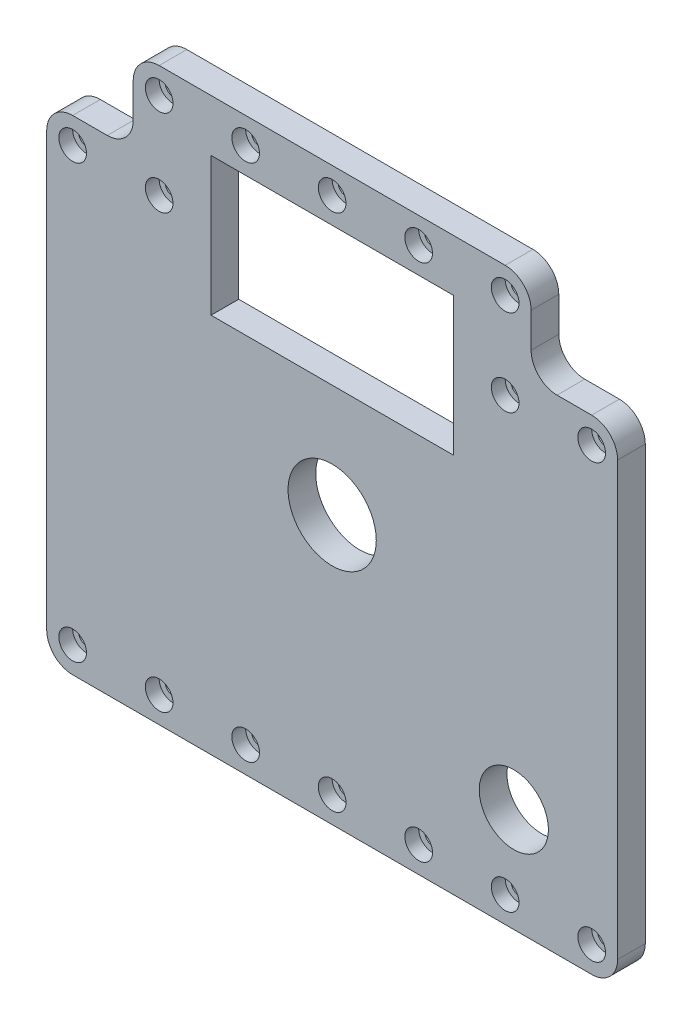
SolidWorks part; units mm, degrees
ref_plane "Front Plane" through (0, 0, 0) normal (0, 0, 1) x (1, 0, 0)
ref_plane "Top Plane" through (0, 0, 0) normal (0, 1, 0) x (1, 0, 0)
ref_plane "Right Plane" through (0, 0, 0) normal (1, 0, 0) x (0, 0, -1)
sketch "Sketch1" plane through (0, 0, 0) normal (0, 0, 1) x (1, 0, 0)
  line L0 (0, 101.5529) -> (0, -112.0648) construction
  line L1 (-50, 67.5) -> (50, 67.5)
  line L2 (57.5, 60) -> (57.5, 50)
  line L3 (65, 42.5) -> (75, 42.5)
  line L4 (82.5, 35) -> (82.5, -90)
  line L5 (75, -97.5) -> (-75, -97.5)
  line L6 (-82.5, -90) -> (-82.5, 35)
  line L7 (-75, 42.5) -> (-65, 42.5)
  line L8 (-57.5, 50) -> (-57.5, 60)
  line L9 (-35, 52.5) -> (-35, 12.5)
  line L10 (-35, 12.5) -> (35, 12.5)
  line L11 (35, 12.5) -> (35, 52.5)
  line L12 (35, 52.5) -> (-35, 52.5)
  arc A0 (-75, 42.5) -> (-82.5, 35) centre (-75, 35) ccw
  arc A1 (-57.5, 50) -> (-65, 42.5) centre (-65, 50) cw
  arc A2 (-50, 67.5) -> (-57.5, 60) centre (-50, 60) ccw
  arc A3 (57.5, 60) -> (50, 67.5) centre (50, 60) ccw
  arc A4 (65, 42.5) -> (57.5, 50) centre (65, 50) cw
  arc A5 (82.5, 35) -> (75, 42.5) centre (75, 35) ccw
  arc A6 (-75, -97.5) -> (-82.5, -90) centre (-75, -90) cw
  arc A7 (82.5, -90) -> (75, -97.5) centre (75, -90) cw
  circle A8 centre (52.5, -67.5) radius 10
  circle A9 centre (0, -20) radius 12.75
  point P15 (-57.5, 42.5)
  point P18 (-57.5, 67.5)
  dimension "D7" = 7.5
  dimension "D8" = 7.5
  dimension "D9" = 7.5
  dimension "D10" = 7.5
  dimension "D11" = 7.5
  dimension "D12" = 7.5
  dimension "D13" = 7.5
  dimension "D14" = 7.5
  dimension "D17" = 20
  dimension "D19" = 25.5
  dimension "D1" = 82.5
  dimension "D2" = 25
  dimension "D3" = 25
  dimension "D4" = 82.5
  dimension "D5" = 165
  dimension "D6" = 67.5
  dimension "D15" = 30
  dimension "D16" = 30
  dimension "D18" = 20
  dimension "D20" = 15
  dimension "D21" = 70
  dimension "D22" = 35
  dimension "D23" = 40
extrude "Boss-Extrude1" add sketch "Sketch1" against normal blind 8
sketch "Sketch2" plane through (0, 0, 0) normal (0, 0, 1) x (1, 0, 0)
  line L0 (-75, 35) -> (-50, 35) construction
  line L1 (-50, 35) -> (-50, 60) construction
  line L2 (-50, 60) -> (50, 60) construction
  line L3 (50, 60) -> (50, 35) construction
  line L4 (50, 35) -> (75, 35) construction
  line L5 (-65, 42.5) -> (-75, 42.5) construction
  line L6 (-57.5, 60) -> (-57.5, 50) construction
  line L7 (50, 67.5) -> (-50, 67.5) construction
  line L8 (57.5, 50) -> (57.5, 60) construction
  line L9 (75, 42.5) -> (65, 42.5) construction
  line L10 (-82.5, 35) -> (-82.5, -90) construction
  line L11 (82.5, -90) -> (82.5, 35) construction
  line L12 (-75, -90) -> (75, -90) construction
  line L13 (-75, -97.5) -> (75, -97.5) construction
  point P10 (-57.5, 55)
  point P17 (70, 42.5)
  point P22 (-25, 60)
  point P23 (-75, 35)
  point P24 (-50, 35)
  point P25 (-50, 60)
  point P26 (0, 60)
  point P27 (25, 60)
  point P29 (50, 60)
  point P30 (50, 35)
  point P31 (75, 35)
  point P35 (-25, -90)
  point P36 (-75, -90)
  point P37 (0, -90)
  point P38 (25, -90)
  point P39 (-50, -90)
  point P40 (50, -90)
  point P41 (75, -90)
  dimension "D1" = 7.5
  dimension "D2" = 7.5
  dimension "D3" = 7.5
  dimension "D4" = 7.5
  dimension "D5" = 7.5
  dimension "D6" = 7.5
  dimension "D7" = 7.5
  dimension "D8" = 25
  dimension "D9" = 25
  dimension "D10" = 25
  dimension "D11" = 7.5
  dimension "D12" = 7.5
  dimension "D13" = 7.5
  dimension "D14" = 25
  dimension "D15" = 25
  dimension "D16" = 25
  dimension "D17" = 25
  dimension "D18" = 25
  dimension "D19" = 25
hole_wizard "CBORE for M4 SHCS1" positions "Sketch2" profile "Sketch3" counterbore size "M4" standard "ANSI Metric" end condition through all
sketch "Sketch3" plane through (75, -90, 0) normal (1, 0, 0) x (0, -1, 0)
  line L0 (0, 0) -> (0, 8)
  line L1 (0, 8) -> (2.25, 8)
  line L3 (2.25, 8) -> (2.25, 4)
  line L4 (2.25, 4) -> (4, 4)
  line L5 (4, 4) -> (4, 0)
  line L7 (4, 0) -> (0, 0)
  line L11 (0, -6.35) -> (0, 107.95) construction
  dimension "Thru Hole Dia." = 4.5
  dimension "Thru Hole Depth" = 8
  dimension "C'Bore Dia." = 8
  dimension "C'Bore Depth" = 4
